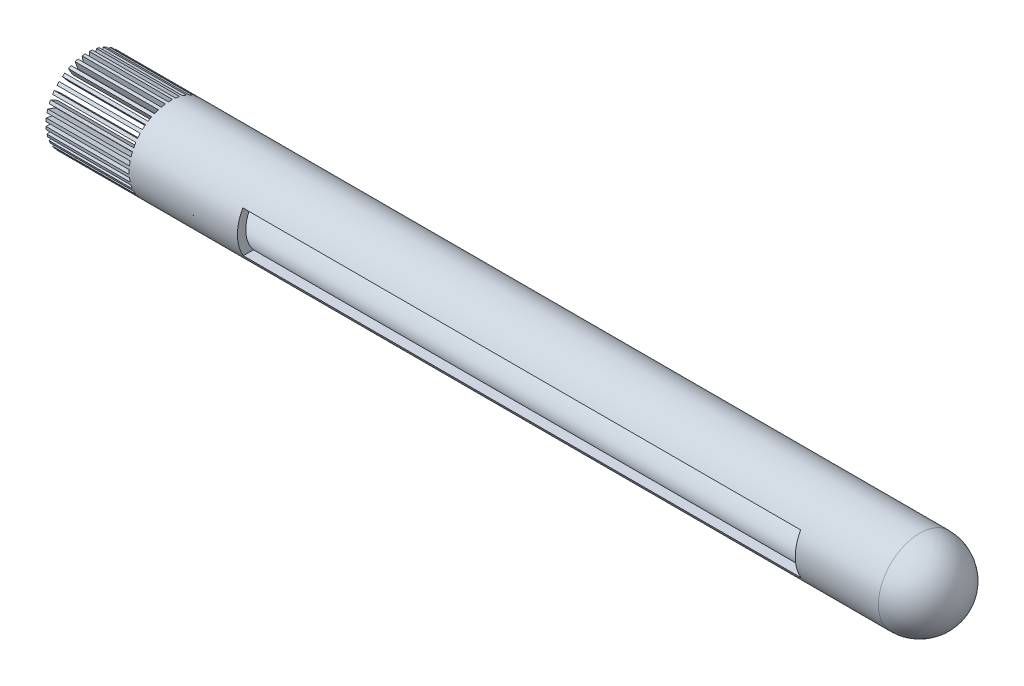
SolidWorks part; units mm, degrees
ref_plane "前视基准面" through (0, 0, 0) normal (0, 0, 1) x (1, 0, 0)
ref_plane "上视基准面" through (0, 0, 0) normal (0, 1, 0) x (1, 0, 0)
ref_plane "右视基准面" through (0, 0, 0) normal (1, 0, 0) x (0, 0, -1)
sketch "草图1"
  line L0 (0, 0) -> (9.8452, 0) construction
  line L5 (-49.9652, 4.9583) -> (50.0221, 4.9583)
  line L7 (-49.9652, -5.0417) -> (50.0348, -5.0417)
  line L8 (-49.9652, 3.9583) -> (50.0197, 3.9583)
  line L9 (-49.9652, -4.0417) -> (50.0311, -4.0417)
  line L10 (-49.9652, 3.9583) -> (-49.9652, 4.9583)
  line L11 (-49.9652, -4.0417) -> (-49.9652, -5.0417)
  arc A1 (50.0348, -5.0417) -> (50.0221, 4.9583) centre (50, -0.0417) ccw
  arc A3 (50.0311, -4.0417) -> (50.0197, 3.9583) centre (50, -0.0417) ccw
  point P0 (0, 0)
  point P15 (0, 0)
  point P16 (0, 0)
  point P17 (-48.3628, 4.1456)
  point P18 (0, 0)
  point P19 (0, 0)
  dimension "D3" = 1
  dimension "D1" = 10
  dimension "D2" = 100
  dimension "D4" = 1
sketch "草图1<5>" plane through (0, 0, 0) normal (0, 0, 1) x (1, 0, 0) same geometry as "草图1"
revolve "旋转9" add sketch "草图1" angle 360 about L0
sketch "草图2" plane through (0, 0, 0) normal (0, 0, 1) x (1, 0, 0)
  line L0 (-49.9652, -4.0417) -> (50.0311, -4.0417) construction
  line L1 (-26.9652, 2.4583) -> (40.0348, 2.4583)
  line L2 (-26.9652, 2.4583) -> (-26.9652, -2.5417)
  line L3 (-26.9652, -2.5417) -> (40.0348, -2.5417)
  line L4 (40.0348, 2.4583) -> (40.0348, -2.5417)
  line L5 (-26.9652, 2.4583) -> (40.0348, -2.5417) construction
  line L6 (-26.9652, -2.5417) -> (40.0348, 2.4583) construction
  line L7 (-49.9652, 3.9583) -> (50.0197, 3.9583) construction
  point P0 (6.5348, -0.0417)
  dimension "D1" = 23
  dimension "D2" = 67
  dimension "D3" = 1.5
  dimension "D4" = 1.5
extrude "切除-拉伸7" cut sketch "草图2" against normal mid plane 10
sketch "草图4" plane through (-49.9652, 0, 0) normal (-1, 0, 0) x (0, 0, 1)
  line L0 (0, 0) -> (5, 0) construction
  line L1 (-5.739, 0.25) -> (-3.261, 0.25)
  line L2 (-5.739, 0.25) -> (-5.739, -0.25)
  line L3 (-5.739, -0.25) -> (-3.261, -0.25)
  line L4 (-3.261, 0.25) -> (-3.261, -0.25)
  line L5 (-5.739, 0.25) -> (-3.261, -0.25) construction
  line L6 (-5.739, -0.25) -> (-3.261, 0.25) construction
  point P0 (-4.5, 0)
  point P7 (0, 0)
  point P8 (0, 0)
  point P9 (0, 0)
  dimension "D1" = 4.5
  dimension "D2" = 0.5
extrude "切除-拉伸8" cut sketch "草图4" against normal blind 10
pattern_circular "阵列(圆周)1" count 36 over 360 about axis through (0, 0, 0) along (-1, 0, 0) of "切除-拉伸8"
